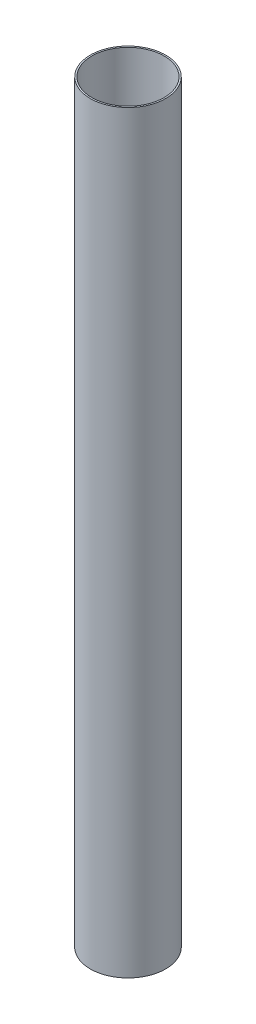
SolidWorks part; units mm, degrees
material "Ceramic Porcelain"
ref_plane "Front" through (0, 0, 0) normal (0, 0, 1) x (1, 0, 0)
ref_plane "Top" through (0, 0, 0) normal (0, 1, 0) x (1, 0, 0)
ref_plane "Right" through (0, 0, 0) normal (1, 0, 0) x (0, 0, -1)
sketch "Sketch1" plane through (0, 0, 0) normal (0, 1, 0) x (1, 0, 0)
  circle A0 centre (0, 0) radius 304.8
  circle A1 centre (0, 0) radius 292.1
  dimension "D1" = 609.6
  dimension "D2" = 584.2
extrude "Boss-Extrude1" add sketch "Sketch1" along normal blind 6096
